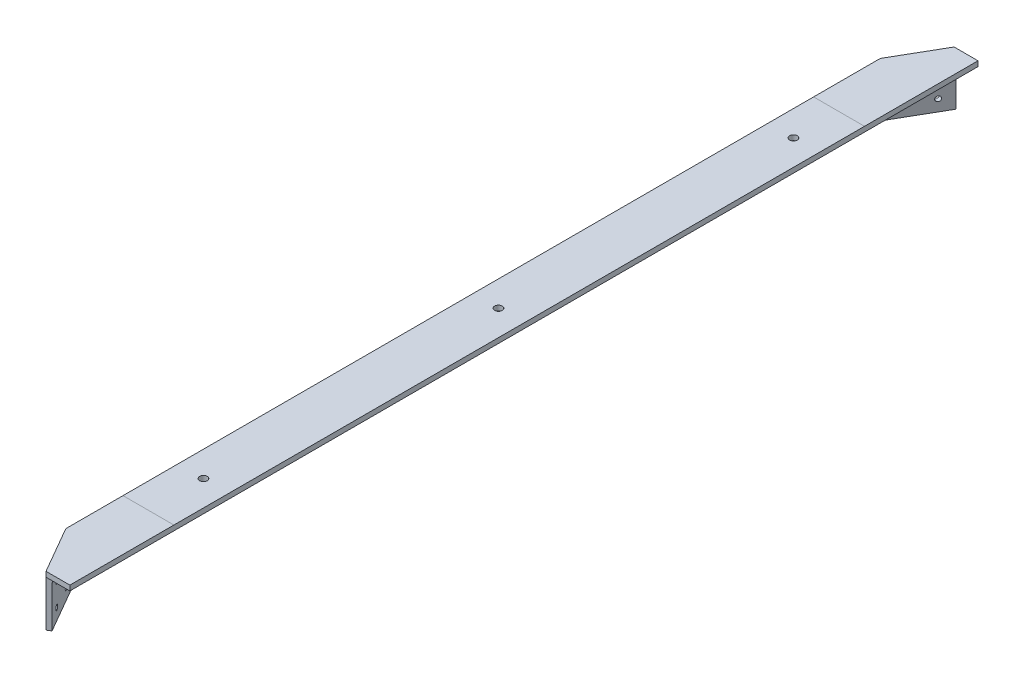
SolidWorks part; units mm, degrees
material "1.0116 (S235J2G3)"
ref_plane "Front Plane" through (0, 0, 0) normal (0, 0, 1) x (1, 0, 0)
ref_plane "Top Plane" through (0, 0, 0) normal (0, 1, 0) x (1, 0, 0)
ref_plane "Right Plane" through (0, 0, 0) normal (1, 0, 0) x (0, 0, -1)
sketch "Sketch1" plane through (0, 0, 0) normal (0, 0, 1) x (1, 0, 0)
  line L0 (-8, 8) -> (72, 8)
  line L1 (72, 8) -> (72, 0)
  line L2 (72, 0) -> (0, 0)
  line L3 (0, 0) -> (0, -72)
  line L4 (0, -72) -> (-8, -72)
  line L5 (-8, -72) -> (-8, 8)
  dimension "D1" = 80
  dimension "D2" = 80
  dimension "D3" = 8
  dimension "D4" = 8
extrude "Boss-Extrude1" add sketch "Sketch1" along normal blind 640
sketch "Sketch3" plane through (0, 0, 0) normal (0, 1, 0) x (1, 0, 0)
  line L0 (-8, -640) -> (34.5, -713.6122)
  line L1 (34.5, -713.6122) -> (72, -713.6122)
  line L2 (72, -713.6122) -> (72, -640)
  line L3 (72, -640) -> (-8, -640)
  line L4 (-8, -640) -> (-8, 0) construction
  dimension "D1" = 210
  dimension "D2" = 85
extrude "Boss-Extrude2" add sketch "Sketch3" along normal blind 8
sketch "Sketch4" plane through (0, 0, 0) normal (0, -1, 0) x (1, 0, 0)
  line L0 (-8, 640) -> (34.5, 713.6122)
  line L1 (34.5, 713.6122) -> (40.5, 710.1481)
  line L2 (40.5, 710.1481) -> (0, 640)
  line L3 (-8, 640) -> (0, 640) construction
  line L4 (0, 640) -> (-8, 640)
  dimension "D1" = 8
extrude "Boss-Extrude3" add sketch "Sketch4" along normal blind 72
sketch "Sketch6" plane through (-277.1281, 0, 160) normal (0.866, 0, -0.5) x (-0.5, 0, -0.866)
  line L0 (-635.2563, -36) -> (-554.2563, -36) construction
  line L1 (-635.2563, -72) -> (-635.2563, 0) construction
  line L2 (-554.2563, -72) -> (-554.2563, 0) construction
  line L3 (-594.7563, 0) -> (-594.7563, -72) construction
  line L4 (-554.2563, 0) -> (-635.2563, 0) construction
  line L5 (-554.2563, -72) -> (-635.2563, -72) construction
  circle A0 centre (-615.0063, -18) radius 4
  circle A1 centre (-574.5063, -18) radius 4
  circle A2 centre (-574.5063, -54) radius 4
  circle A3 centre (-615.0063, -54) radius 4
  dimension "D1" = 20.25
  dimension "D3" = 8
  dimension "D2" = 18
extrude "Cut-Extrude1" cut sketch "Sketch6" against normal blind 8
fillet "Fillet1" radius 10 2 edges at (-8, -32, 640) (0, -36, 640)
fillet "Fillet2" radius 8 3 edges at (0, 0, 318.6603) (0.3407, 0, 639.9087) (20.9199, 0, 676.2343)
mirror "Mirror1" about plane through (0, 0, 0) normal (0, 0, 1) of "Boss-Extrude1", "Boss-Extrude2", "Boss-Extrude3", "Cut-Extrude1", "Fillet1", "Fillet2"
sketch "Sketch7" plane through (0, 8, 0) normal (0, 1, 0) x (1, 0, 0)
  line L0 (-8, 535.2362) -> (72, 535.2362)
  line L1 (-8, -637.3205) -> (-8, 637.3205) construction
  line L2 (72, -713.6122) -> (72, 713.6122) construction
  line L3 (72, 535.2362) -> (72, -550.1105)
  line L4 (72, -550.1105) -> (-8, -550.1105)
  line L5 (-8, -550.1105) -> (-8, 535.2362)
  dimension "D1" = 102.0843
  dimension "D2" = 87.21
split line "Split Line1"
sketch "Sketch8" plane through (0, 8, 0) normal (0, 1, 0) x (1, 0, 0)
  line L0 (34.5, -713.6122) -> (72, -713.6122) construction
  line L1 (-8, -550.1105) -> (-8, 535.2362) construction
  line L2 (34.5, 713.6122) -> (72, 713.6122) construction
  circle A0 centre (32, 463.6122) radius 6
  circle A1 centre (32, 0) radius 6
  circle A2 centre (32, -463.6122) radius 6
  dimension "D1" = 12
  dimension "D2" = 12
  dimension "D3" = 12
  dimension "D4" = 250
  dimension "D5" = 40
  dimension "D6" = 40
  dimension "D7" = 40
  dimension "D8" = 250
  dimension "D9" = 713.6122
extrude "Cut-Extrude2" cut sketch "Sketch8" against normal blind 8
